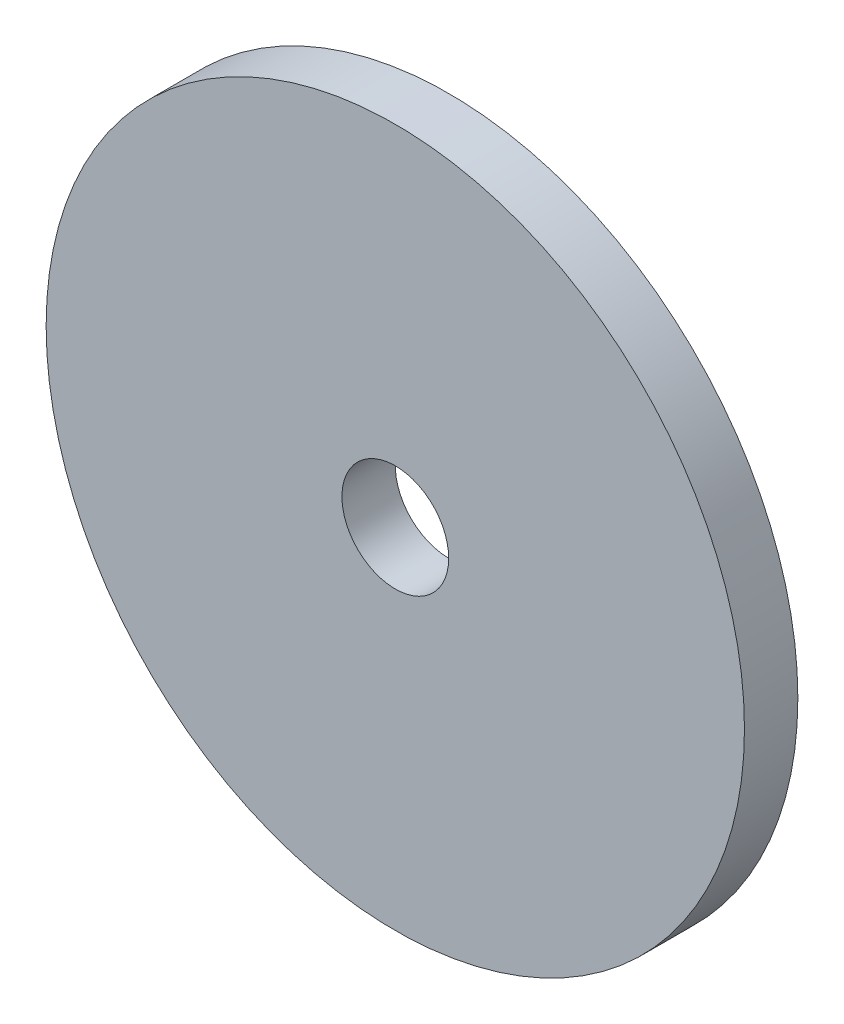
SolidWorks part; units mm, degrees
ref_plane "Front Plane" through (0, 0, 0) normal (0, 0, 1) x (1, 0, 0)
ref_plane "Top Plane" through (0, 0, 0) normal (0, 1, 0) x (1, 0, 0)
ref_plane "Right Plane" through (0, 0, 0) normal (1, 0, 0) x (0, 0, -1)
sketch "Sketch1" plane through (0, 0, 0) normal (0, 0, 1) x (1, 0, 0)
  circle A0 centre (0, 0) radius 41.529
  circle A1 centre (0, 0) radius 6.35
  dimension "D1" = 83.058
  dimension "D2" = 12.7
extrude "Boss-Extrude1" add sketch "Sketch1" along normal blind 6.35
